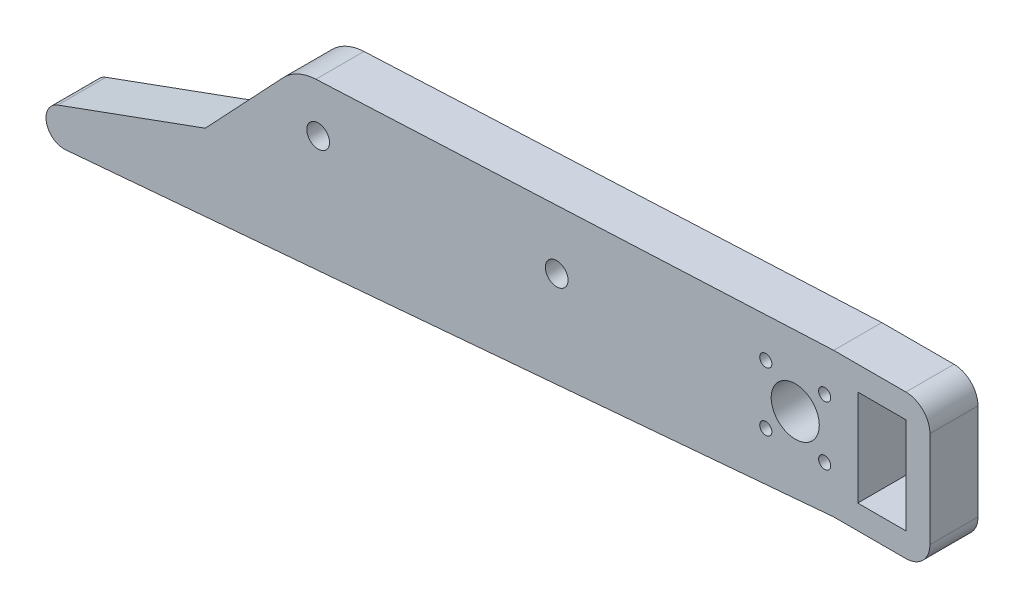
SolidWorks part; units mm, degrees
ref_plane "Front Plane" through (0, 0, 0) normal (0, 0, 1) x (1, 0, 0)
ref_plane "Top Plane" through (0, 0, 0) normal (0, 1, 0) x (1, 0, 0)
ref_plane "Right Plane" through (0, 0, 0) normal (1, 0, 0) x (0, 0, -1)
sketch "Sketch1" plane through (0, 0, 0) normal (0, 0, 1) x (1, 0, 0)
  line L0 (27.6069, 3.8891) -> (35.3851, -3.8891) construction
  line L1 (0, -55) -> (0, 55) construction
  line L2 (27.6069, -3.8891) -> (35.3851, 3.8891) construction
  line L3 (-1001.9207, 0) -> (48998.0793, 0) construction
  line L4 (-969.6313, -19.05) -> (49030.3687, -19.05) construction
  line L5 (36.576, 9.525) -> (49.276, 9.525)
  line L6 (39.751, 6.35) -> (46.101, 6.35)
  line L7 (39.751, 6.35) -> (39.751, -6.35)
  line L8 (39.751, -6.35) -> (46.101, -6.35)
  line L9 (46.101, 6.35) -> (46.101, -6.35)
  line L10 (39.751, 6.35) -> (46.101, -6.35) construction
  line L11 (39.751, -6.35) -> (46.101, 6.35) construction
  line L13 (36.576, -9.525) -> (49.276, -9.525)
  line L14 (36.576, 0) -> (36.576, -9.525) construction
  line L15 (49.276, 9.525) -> (49.276, -9.525)
  line L21 (36.576, 9.525) -> (36.576, 0) construction
  line L22 (36.576, 9.525) -> (36.576, -9.525) construction
  line L23 (-46.398, -6.562) -> (-80.7085, -19.05) construction
  line L24 (49.276, 9.525) -> (49.276, -9.525) construction
  line L25 (36.576, 9.525) -> (-31.7912, 6.3431)
  line L26 (-36.1188, 4.3534) -> (-46.398, -6.562)
  line L27 (-46.398, -6.562) -> (-65.8615, -13.6461)
  line L28 (-64.8428, -18.2563) -> (36.576, -9.525)
  circle A0 centre (31.496, 0) radius 3.175
  circle A1 centre (27.6069, 3.8891) radius 0.8
  circle A2 centre (35.3851, -3.8891) radius 0.8
  circle A4 centre (-31.496, 0) radius 1.5
  circle A5 centre (35.3851, 3.8891) radius 0.8
  circle A6 centre (27.6069, -3.8891) radius 0.8
  circle A7 centre (31.496, 0) radius 19.05 construction
  circle A8 centre (-31.496, 0) radius 19.05 construction
  arc A16 (-31.7912, 6.3431) -> (-36.1188, 4.3534) centre (-31.496, 0) ccw
  circle A17 centre (-29.9085, 22.225) radius 38.1 construction
  arc A18 (-65.8615, -13.6461) -> (-64.8428, -18.2563) centre (-65.0471, -15.8838) ccw
  arc A19 (-37.846, 0) -> (-25.146, 0) centre (-31.496, 0) ccw construction
  arc A21 (-25.146, 0) -> (-31.7912, 6.3431) centre (-31.496, 0) ccw construction
  arc A22 (-36.1188, 4.3534) -> (-37.846, 0) centre (-31.496, 0) ccw construction
  circle A23 centre (0, 0) radius 1.5
  point P6 (31.496, 0)
  point P17 (31.496, 0)
  point P33 (42.926, 0)
  point P43 (-58.8467, -15.875)
  point P44 (-44.366, -6.35)
  point P45 (0, 0)
  point P47 (0, 0)
  point P51 (-29.9085, -15.875)
  point P52 (-68.0085, 22.225)
  dimension "D1" = 6.35
  dimension "D3" = 62.992
  dimension "D4" = 1.6
  dimension "D7" = 38.1
  dimension "D10" = 12.7
  dimension "D11" = 36.5125
  dimension "D16" = 1.5875
  dimension "D18" = 76.2
  dimension "D6" = 3
  dimension "D9" = 12.7
  dimension "D19" = 4.7625
  dimension "D2" = 11
  dimension "D5" = 45
  dimension "D8" = 20
  dimension "D12" = 6.35
  dimension "D13" = 12.7
  dimension "D15" = 11.43
  dimension "D17" = 3.175
  dimension "D20" = 1.5875
  dimension "D14" = 3.175
extrude "Boss-Extrude1" add sketch "Sketch1" along normal mid plane 6.35 contours L27 A18 L28 L13 L15 L5 L25 A16 L26 A4 A2 A1 A0 L6 L9 L8 L7 A5 A6 region at (-5.0143, -3.6936, 0)
fillet "Fillet1" radius 3.175 2 edges at (49.276, -9.525, 0) (49.276, 9.525, 0)
